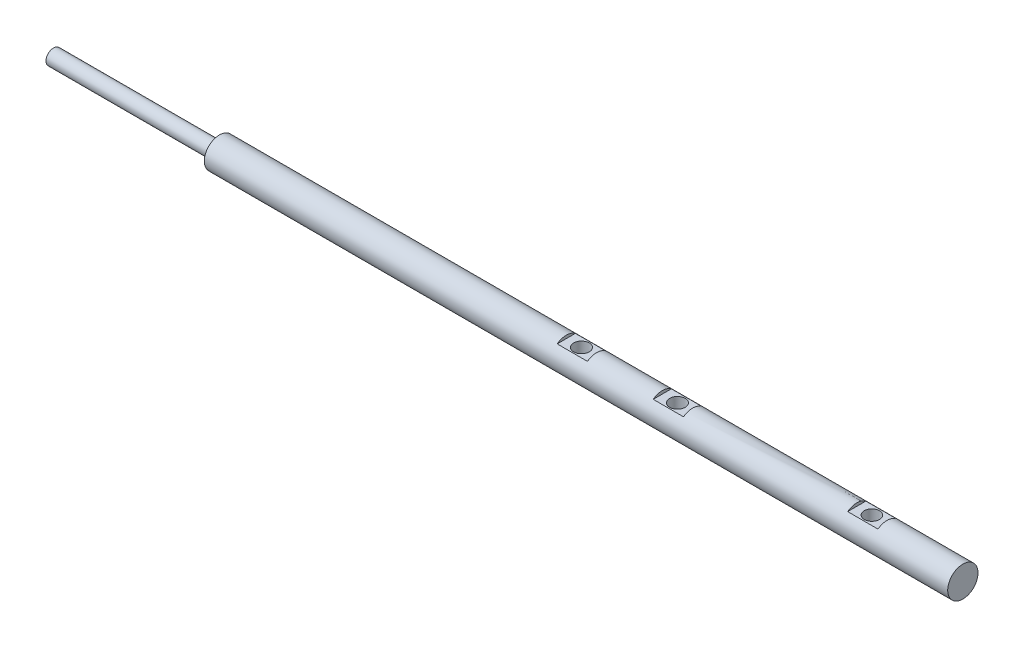
SolidWorks part; units mm, degrees
ref_plane "Front Plane" through (0, 0, 0) normal (0, 0, 1) x (1, 0, 0)
ref_plane "Top Plane" through (0, 0, 0) normal (0, 1, 0) x (1, 0, 0)
ref_plane "Right Plane" through (0, 0, 0) normal (1, 0, 0) x (0, 0, -1)
sketch "Sketch2" plane through (0, 0, 0) normal (1, 0, 0) x (0, 0, -1)
  circle A0 centre (0, 0) radius 3.175
  dimension "D1" = 6.35
extrude "Main Shaft" add sketch "Sketch2" along normal mid plane 190.5
sketch "Sketch3" plane through (0, 0, 0) normal (0, 1, 0) x (1, 0, 0)
  line L0 (-95.25, 0) -> (95.25, 0) construction
  line L1 (95.25, -3.175) -> (95.25, 3.175) construction
  line L2 (25.4, -8.7177) -> (25.4, 8.7177) construction
  circle A0 centre (15.3416, 0) radius 1.632
  circle A1 centre (35.4584, 0) radius 1.6319
  point P6 (0, 0)
  point P10 (25.4, 0)
  dimension "D2" = 3.2639
  dimension "D3" = 20.1168
  dimension "D1" = 120.65
extrude "Pin Holes Cut" cut sketch "Sketch3" against normal through all both and the other way through all
sketch "Sketch5" plane through (0, 0, 0) normal (0, 0, 1) x (1, 0, 0)
  line L0 (16.9735, 3.175) -> (13.7096, 3.175)
  line L1 (33.8265, 3.175) -> (16.9735, 3.175) construction
  line L2 (13.7097, 3.175) -> (-95.25, 3.175) construction
  line L3 (12.1666, 3.175) -> (18.5166, 3.175)
  line L4 (12.1666, 3.175) -> (12.1666, 2.54)
  line L5 (12.1666, 2.54) -> (18.5166, 2.54)
  line L6 (18.5166, 3.175) -> (18.5166, 2.54)
  line L7 (16.9735, -3.175) -> (33.8265, -3.175) construction
  line L9 (16.9735, -3.175) -> (33.8265, -3.175)
  line L10 (25.4, 6.7576) -> (25.4, -3.175)
  line L11 (38.6333, 2.54) -> (32.2833, 2.54)
  line L12 (32.2833, 3.175) -> (32.2833, 2.54)
  line L13 (38.6333, 3.175) -> (32.2833, 3.175)
  line L14 (38.6333, 3.175) -> (38.6333, 2.54)
  spline S0 degree 2 poles (16.9735, 3.175) (15.3416, 2.3362) (13.7096, 3.175) knots 0 0 0 1 1 1 weights 0.001543 0.003175 0.004807 construction
  point P0 (13.7096, 3.175)
  point P10 (15.3416, 3.175)
  point P15 (15.3416, 2.54)
  point P18 (25.4, -3.175)
  point P20 (25.4, 6.7576)
  point P26 (32.2834, 3.175)
  point P27 (32.2294, 3.2963)
  point P28 (0, 0)
  point P29 (25.4, 6.7576)
  dimension "D1" = 0.635
  dimension "D2" = 6.35
extrude "Flat for drilling Cut" cut sketch "Sketch5" against normal through all both and the other way through all contours L6 L3 L0 L4 L5 | L14 L13 L12 L11 region at (15.3416, 2.8575, 0) region at (35.4583, 2.8575, 0)
sketch "Sketch6" plane through (-95.25, 0, 0) normal (-1, 0, 0) x (0, 0, 1)
  circle A0 centre (0, 0) radius 1.5875
  circle A1 centre (0, 0) radius 3.175
  circle A2 centre (0, 0) radius 3.175
  dimension "D2" = 3.175
  dimension "D1" = 0
extrude "1/8 Cut" cut sketch "Sketch6" against normal blind 34.7548 and the other way through all
sketch "Sketch7" plane through (0, 0, 0) normal (0, 1, 0) x (1, 0, 0)
  line L0 (-95.25, 1.5875) -> (-95.25, -1.5875) construction
  line L1 (73.025, -6.587) -> (79.375, -6.587)
  line L2 (73.025, -6.587) -> (73.025, 6.587)
  line L3 (73.025, 6.587) -> (79.375, 6.587)
  line L4 (79.375, -6.587) -> (79.375, 6.587)
  line L5 (73.025, -6.587) -> (79.375, 6.587) construction
  line L6 (73.025, 6.587) -> (79.375, -6.587) construction
  circle A0 centre (76.2, 0) radius 1.6
  point P6 (91.5326, -7.3378)
  point P7 (0, 0)
  dimension "D1" = 171.45
  dimension "D2" = 3.2
  dimension "D3" = 6.35
extrude "Cut-Extrude1" cut sketch "Sketch7" against normal through all both and the other way through all contours A0 region at (76.2, 0, 0)
extrude "Cut-Extrude2" cut sketch "Sketch7<3>" along normal through all from offset 2.54
sketch "Sketch7<3>" plane through (0, 0, 0) normal (0, 1, 0) x (1, 0, 0) same geometry as "Sketch7"
